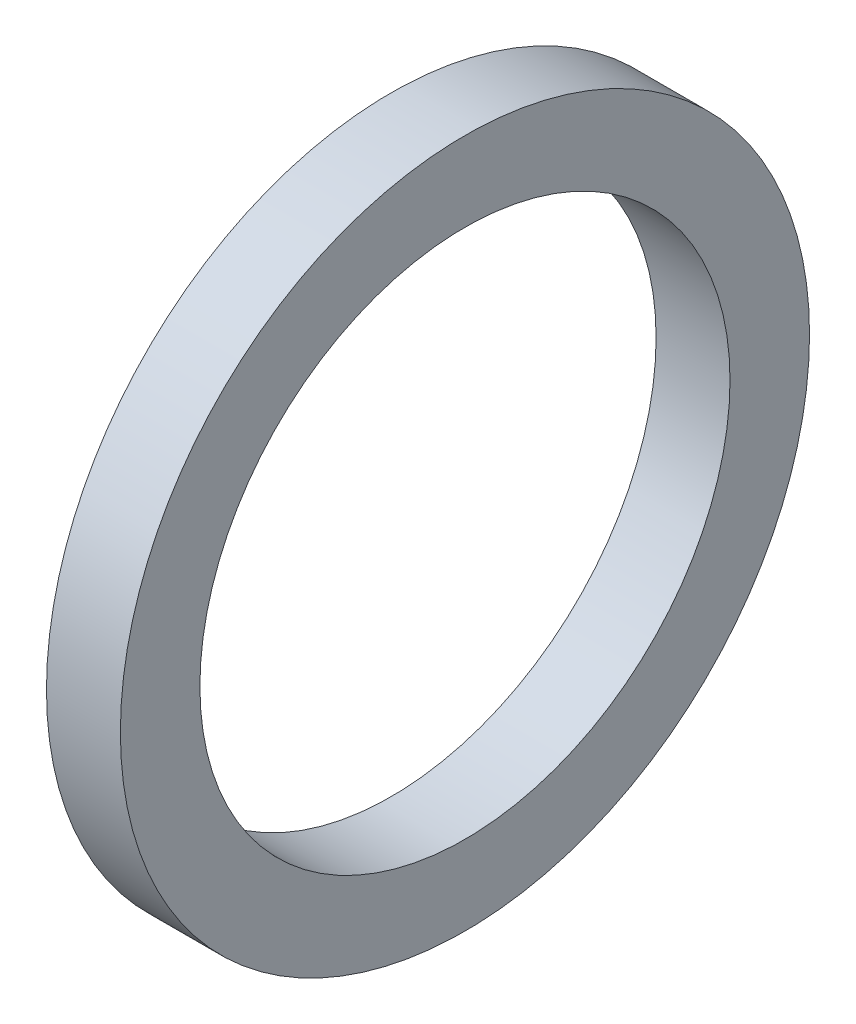
SolidWorks part; units mm, degrees
ref_plane "Front Plane" through (0, 0, 0) normal (0, 0, 1) x (1, 0, 0)
ref_plane "Top Plane" through (0, 0, 0) normal (0, 1, 0) x (1, 0, 0)
ref_plane "Right Plane" through (0, 0, 0) normal (1, 0, 0) x (0, 0, -1)
sketch "Sketch2" plane through (0, 0, 0) normal (0, 0, 1) x (1, 0, 0)
  line L0 (0, 0) -> (58.591, 0) construction
  line L2 (0, 0) -> (18.4, 0)
  line L3 (0, 0) -> (0, 2.5)
  line L4 (0, 2.5) -> (18.4, 2.5)
  line L5 (18.4, 0) -> (18.4, 2.5)
  line L6 (6.0094, 2.5) -> (6.0094, 6)
  line L11 (6.0094, 6) -> (9.9794, 6)
  line L16 (12.9794, 6) -> (12.9794, 3)
  line L17 (12.9794, 3) -> (13.6398, 3)
  line L18 (13.6398, 3) -> (13.6398, 2.5)
  line L19 (13.6398, 2.5) -> (6.0094, 2.5)
  line L22 (13.6398, 2.5) -> (16.1198, 2.5)
  line L23 (13.6398, 2.5) -> (13.6398, 4)
  line L24 (13.6398, 4) -> (16.1198, 4)
  line L25 (16.1198, 2.5) -> (16.1198, 4)
  line L27 (6.0094, 6) -> (9.9794, 6)
  line L28 (6.0094, 6) -> (6.0094, 9)
  line L29 (6.0094, 9) -> (9.9794, 9)
  line L30 (9.9794, 6) -> (9.9794, 9)
  line L31 (6.0094, 9) -> (6.0094, 8.25)
  line L32 (6.0094, 8.25) -> (5.0094, 8.25)
  line L33 (8.6609, 22.001) -> (8.6609, 12.476) construction
  line L34 (5.0094, 12.476) -> (12.3124, 12.476)
  line L35 (9.9794, 9) -> (12.3124, 9)
  line L36 (5.0094, 7.9375) -> (1.8344, 7.9375)
  line L37 (5.0094, 8.25) -> (5.0094, 12.476)
  line L38 (5.0094, 7.9375) -> (5.0094, 13.9365)
  line L39 (5.0094, 13.9365) -> (1.8344, 13.9365)
  line L40 (1.8344, 7.9375) -> (1.8344, 13.9365)
  line L41 (5.0094, 22.001) -> (12.3124, 22.001)
  line L42 (5.0094, 22.001) -> (5.0094, 30.1625)
  line L43 (5.0094, 30.1625) -> (12.3124, 30.1625)
  line L44 (12.3124, 22.001) -> (12.3124, 30.1625)
  line L49 (16.6398, 22.001) -> (16.6398, 7.5)
  line L51 (23.0198, 7.5) -> (23.0198, 6.5)
  line L54 (16.1198, 4) -> (13.6398, 4)
  line L56 (18.0398, 7.5) -> (23.0198, 7.5)
  line L57 (13.3124, 22.001) -> (16.6398, 22.001)
  line L58 (16.1198, 3.5) -> (20.0198, 3.5)
  line L59 (29.9098, 14) -> (26.9098, 11)
  line L60 (4.0094, 31.75) -> (18.0398, 31.75)
  line L61 (18.0398, 7.5) -> (23.0198, 7.5)
  line L62 (18.0398, 7.5) -> (18.0398, 12)
  line L63 (18.0398, 12) -> (23.0198, 12)
  line L64 (23.0198, 7.5) -> (23.0198, 12)
  line L65 (18.0398, 31.75) -> (18.0398, 12)
  line L66 (23.0198, 11) -> (26.9098, 11)
  line L67 (34.8098, 23) -> (31.3098, 19.5)
  line L68 (35.8098, 31) -> (38.7998, 33.99)
  line L69 (29.9098, 14) -> (29.9098, 15)
  line L70 (29.9098, 15) -> (22.9398, 15)
  line L71 (22.9398, 15) -> (21.0398, 15)
  line L72 (18.0398, 7.5) -> (16.6398, 7.5)
  line L73 (21.0398, 15) -> (21.0398, 43)
  line L74 (19.5798, 40) -> (9.6198, 40)
  line L75 (9.6198, 40) -> (4.0094, 40)
  line L76 (21.0398, 43) -> (19.5798, 43)
  line L77 (22.9398, 15) -> (29.9098, 15)
  line L78 (22.9398, 15) -> (22.9398, 21)
  line L79 (22.9398, 21) -> (29.9098, 21)
  line L80 (29.9098, 15) -> (29.9098, 21)
  line L81 (9.6198, 40) -> (19.5798, 40)
  line L82 (9.6198, 40) -> (9.6198, 50)
  line L83 (9.6198, 50) -> (19.5798, 50)
  line L84 (19.5798, 40) -> (19.5798, 50)
  line L85 (4.0094, 40) -> (4.0094, 31.75)
  line L86 (12.9794, 3) -> (12.9794, 2.5)
  line L87 (31.3098, 19.5) -> (29.9098, 19.5)
  line L88 (21.4694, 63.5) -> (21.4694, 51.308)
  line L89 (21.4694, 63.5) -> (25.9398, 63.5)
  line L90 (25.9398, 63.5) -> (25.9398, 25)
  line L91 (27.8398, 25) -> (25.9398, 25)
  line L92 (9.6198, 48) -> (8.1598, 48)
  line L93 (8.1598, 48) -> (8.1598, 53.476)
  line L94 (8.1598, 53.476) -> (19.5798, 53.476)
  line L95 (19.5798, 53.476) -> (19.5798, 50)
  line L96 (13.8698, 63.001) -> (13.8698, 53.476) construction
  line L97 (8.1598, 63.001) -> (19.5798, 63.001)
  line L98 (8.1598, 63.001) -> (8.1598, 68.2625)
  line L99 (8.1598, 68.2625) -> (19.5798, 68.2625)
  line L100 (19.5798, 63.001) -> (19.5798, 68.2625)
  line L101 (12.9794, 6) -> (11.9794, 6)
  line L102 (8.1598, 44.825) -> (4.9848, 44.825)
  line L103 (8.1598, 44.825) -> (8.1598, 54.9365)
  line L104 (8.1598, 54.9365) -> (4.9848, 54.9365)
  line L106 (9.9794, 6) -> (10.8794, 6)
  line L107 (27.8398, 25) -> (34.8098, 25)
  line L108 (34.8098, 25) -> (34.8098, 23)
  line L109 (0, 0) -> (-2, 0)
  line L110 (0, 0) -> (0, 11)
  line L111 (27.8398, 25) -> (34.8098, 25)
  line L112 (27.8398, 25) -> (27.8398, 32.5)
  line L113 (27.8398, 32.5) -> (34.8098, 32.5)
  line L114 (34.8098, 25) -> (34.8098, 32.5)
  line L115 (35.8098, 31) -> (34.8098, 31)
  line L116 (27.8398, 32.5) -> (27.8398, 64.5)
  line L117 (20.5373, 74.025) -> (6.2023, 74.025)
  line L118 (6.2023, 74.025) -> (6.2023, 76.2)
  line L119 (38.7998, 47.29) -> (30.8398, 55.25)
  line L120 (0, 11) -> (-2, 11)
  line L121 (38.7998, 43.815) -> (30.8623, 43.815)
  line L123 (-4.8152, 69.85) -> (1.5348, 76.2)
  line L124 (38.7998, 47.29) -> (38.7998, 33.99)
  line L125 (-2, 0) -> (-2, 11)
  line L126 (38.7998, 37.465) -> (30.8623, 37.465)
  line L127 (30.8623, 43.815) -> (30.8623, 37.465)
  line L128 (6.0094, 2.5) -> (6.0094, 0)
  line L129 (-0.0152, 63.5) -> (-0.0152, 30)
  line L132 (4.9848, 63.5) -> (-0.0152, 63.5)
  line L136 (-1.8152, 30) -> (-11.7752, 30)
  line L138 (-13.7752, 25.4) -> (-2, 25.4)
  line L139 (-2, 25.4) -> (-2, 11.5)
  line L140 (27.8398, 64.5) -> (20.5373, 64.5)
  line L141 (-1.8152, 30) -> (-11.7752, 30)
  line L142 (-1.8152, 30) -> (-1.8152, 39)
  line L143 (-1.8152, 39) -> (-11.7752, 39)
  line L144 (-11.7752, 30) -> (-11.7752, 39)
  line L145 (20.5373, 64.5) -> (20.5373, 74.025)
  line L146 (-12.7752, 37) -> (-12.7752, 47.29)
  line L147 (-12.7752, 37) -> (-11.7752, 37)
  line L148 (30.8398, 55.25) -> (30.8398, 76.2)
  line L149 (11.9794, 6) -> (11.9794, 5.45)
  line L154 (-2, 11.5) -> (0.5, 11.5)
  line L155 (4.9848, 60.6197) -> (24.0348, 60.6197)
  line L160 (4.9848, 60.6197) -> (4.9848, 55.8572)
  line L161 (4.9848, 55.8572) -> (24.0348, 55.8572)
  line L166 (24.0348, 60.6197) -> (24.0348, 55.8572)
  line L167 (4.9848, 60.6197) -> (24.0348, 55.8572) construction
  line L172 (4.9848, 55.8572) -> (24.0348, 60.6197) construction
  line L173 (24.0348, 62.2072) -> (25.9398, 62.2072)
  line L174 (11.9794, 5.45) -> (10.8794, 5.45)
  line L175 (10.8794, 6) -> (10.8794, 5.45)
  line L176 (24.0348, 62.2072) -> (24.0348, 54.2697)
  line L177 (24.0348, 54.2697) -> (25.9398, 54.2697)
  line L178 (25.9398, 62.2072) -> (25.9398, 54.2697)
  line L179 (24.0348, 62.2072) -> (25.9398, 54.2697) construction
  line L180 (24.0348, 54.2697) -> (25.9398, 62.2072) construction
  line L181 (3, 19.6197) -> (15.7, 19.6197)
  line L182 (3, 19.6197) -> (3, 14.8572)
  line L183 (3, 14.8572) -> (15.7, 14.8572)
  line L184 (15.7, 19.6197) -> (15.7, 14.8572)
  line L185 (3, 19.6197) -> (15.7, 14.8572) construction
  line L186 (3, 14.8572) -> (15.7, 19.6197) construction
  line L187 (15.7, 21.2072) -> (16.6398, 21.2072)
  line L188 (15.7, 21.2072) -> (15.7, 13.2697)
  line L189 (15.7, 13.2697) -> (16.6398, 13.2697)
  line L190 (16.6398, 21.2072) -> (16.6398, 13.2697)
  line L191 (15.7, 21.2072) -> (16.6398, 13.2697) construction
  line L192 (15.7, 13.2697) -> (16.6398, 21.2072) construction
  line L193 (0.5, 11.5) -> (0.5, 6.9375)
  line L194 (0.5, 6.9375) -> (1.8344, 6.9375)
  line L195 (23.0198, 6.5) -> (20.0198, 3.5)
  line L196 (4.9848, 63.5) -> (4.9848, 54.9365)
  line L197 (3, 43.825) -> (4.9848, 43.825)
  line L198 (1.8344, 6.9375) -> (1.8344, 7.9375)
  line L199 (6.0094, 0) -> (12.9794, 0)
  line L200 (12.9794, 0) -> (12.9794, 2.5)
  line L201 (18.0398, 31.75) -> (18.0398, 35.875)
  line L202 (18.0398, 35.875) -> (21.0398, 35.875)
  line L203 (30.8398, 76.2) -> (6.2023, 76.2)
  line L204 (2.7573, 69.85) -> (7.2023, 69.85) construction
  line L205 (7.2023, 67.4688) -> (26.2523, 67.4688)
  line L206 (7.2023, 74.025) -> (7.2023, 64.5)
  line L207 (7.2023, 64.5) -> (-1.8152, 64.5)
  line L208 (-1.8152, 64.5) -> (-1.8152, 39)
  line L209 (-12.7752, 47.29) -> (-4.8152, 55.25)
  line L210 (-4.8152, 55.25) -> (-4.8152, 69.85)
  line L211 (7.2023, 67.4688) -> (7.2023, 72.2312)
  line L212 (7.2023, 72.2312) -> (26.2523, 72.2313)
  line L213 (26.2523, 67.4688) -> (26.2523, 72.2313)
  line L214 (26.2523, 73.8187) -> (30.8398, 73.8187)
  line L215 (26.2523, 73.8187) -> (26.2523, 65.8813)
  line L216 (26.2523, 65.8813) -> (30.8398, 65.8813)
  line L217 (30.8398, 73.8187) -> (30.8398, 65.8813)
  line L218 (2.7573, 72.2313) -> (24.9823, 72.2313)
  line L219 (2.7573, 72.2313) -> (2.7573, 67.4687)
  line L220 (2.7573, 67.4687) -> (24.9823, 67.4687)
  line L221 (24.9823, 72.2313) -> (24.9823, 67.4687)
  line L222 (24.9823, 69.85) -> (20.5373, 69.85) construction
  line L223 (21.4694, 51.308) -> (22.9398, 51.308)
  line L224 (22.9398, 51.308) -> (22.9398, 21)
  line L225 (13.6398, 4) -> (13.6398, 12.2697)
  line L226 (13.6398, 12.2697) -> (13.3124, 12.2697)
  line L227 (13.3124, 12.2697) -> (13.3124, 22.001)
  line L228 (12.3124, 9) -> (12.3124, 12.476)
  line L229 (-1.8152, 30) -> (-0.0152, 30)
  line L230 (8.1598, 65.6317) -> (2.7573, 65.6317) construction
  line L231 (19.5798, 65.6317) -> (24.9823, 65.6317) construction
  line L232 (1.5348, 76.2) -> (6.2023, 76.2)
  line L233 (-11.7752, 30) -> (-13.7752, 30)
  line L234 (-13.7752, 30) -> (-13.7752, 25.4)
  line L235 (3, 13.9365) -> (3, 43.825)
  line L236 (4.9848, 54.9365) -> (4.9848, 44.825)
  line L237 (4.9848, 43.825) -> (4.9848, 44.825)
  circle A0 centre (26.8898, 25.95) radius 0.95
  circle A1 centre (21.9898, 15.95) radius 0.95
  circle A2 centre (17.3398, 8.2) radius 0.7
  circle A3 centre (10.4294, 6.45) radius 0.45
  circle A4 centre (-0.9152, 30.9) radius 0.9
  point P7 (24.9873, 58.2385)
  point P131 (16.1699, 17.2385)
  point P135 (14.5098, 58.2385)
  point P146 (9.35, 17.2385)
sketch "Sketch3" plane through (0, 0, 0) normal (0, 0, 1) x (1, 0, 0)
  line L0 (27.8398, 25) -> (34.8098, 25) construction
  line L1 (27.8398, 25) -> (27.8398, 32.5) construction
  line L2 (34.8098, 25) -> (34.8098, 32.5) construction
  line L3 (27.8398, 32.5) -> (34.8098, 32.5) construction
  line L4 (27.8398, 25) -> (34.8098, 25)
  line L5 (27.8398, 25) -> (27.8398, 32.5)
  line L6 (34.8098, 25) -> (34.8098, 32.5)
  line L7 (27.8398, 32.5) -> (34.8098, 32.5)
revolve "Revolve1" add sketch "Sketch3" angle 360 about L0
